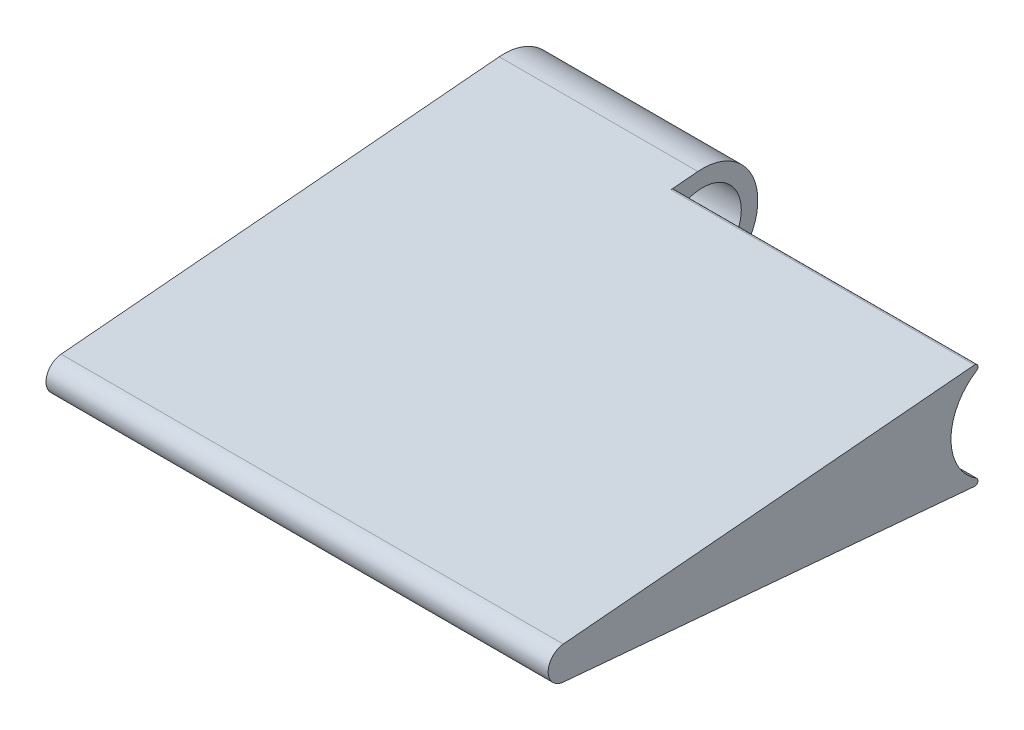
SolidWorks part; units mm, degrees
ref_plane "Front Plane" through (0, 0, 0) normal (0, 0, 1) x (1, 0, 0)
ref_plane "Top Plane" through (0, 0, 0) normal (0, 1, 0) x (1, 0, 0)
ref_plane "Right Plane" through (0, 0, 0) normal (1, 0, 0) x (0, 0, -1)
sketch "Sketch1" plane through (0, 0, 0) normal (1, 0, 0) x (0, 0, -1)
  line L0 (-40.1313, 1.4942) -> (-0.4375, 4.9808)
  line L1 (-40.1313, -1.4942) -> (-0.4375, -4.9808)
  circle A0 centre (0, 0) radius 5
  circle A1 centre (0, 0) radius 3.5
  circle A2 centre (-40, 0) radius 1.5
  dimension "D1" = 7
  dimension "D2" = 10
  dimension "D3" = 3
  dimension "D4" = 40
extrude "Boss-Extrude1" add sketch "Sketch1" along normal blind 27.5 contours A2 L1 A0 L0 | A2 region at (0, 0, 18.6105) region at (0, 0, 40)
extrude "Boss-Extrude2" add sketch "Sketch1<3>" against normal blind 18 contours A2 L1 A0 L0 | A2 | A0 A1 region at (0, 0, 18.6105) region at (0, 0, 40) region at (0, 3.5827, -3.2818)
sketch "Sketch1<3>" plane through (0, 0, 0) normal (1, 0, 0) x (0, 0, -1) same geometry as "Sketch1"
fillet "Fillet1" radius 0.3 2 edges at (13.75, -4.9808, 0.4375) (13.75, 4.9808, 0.4375)
sketch "Sketch2" plane through (0, 0, 0) normal (0, 0, 1) x (1, 0, 0)
  line L0 (-18, 5) -> (-18, -5) construction
  line L1 (0, -6.1303) -> (-18, -6.1303)
  line L2 (0, -6.1303) -> (0, -1.8)
  line L3 (0, -1.8) -> (-18, -1.8)
  line L4 (-18, -6.1303) -> (-18, -1.8)
  line L5 (-18, -5) -> (0, -5) construction
  dimension "D1" = 18
  dimension "D2" = 3.2
extrude "Cut-Extrude1" cut sketch "Sketch2" along normal blind 48 from offset 6
